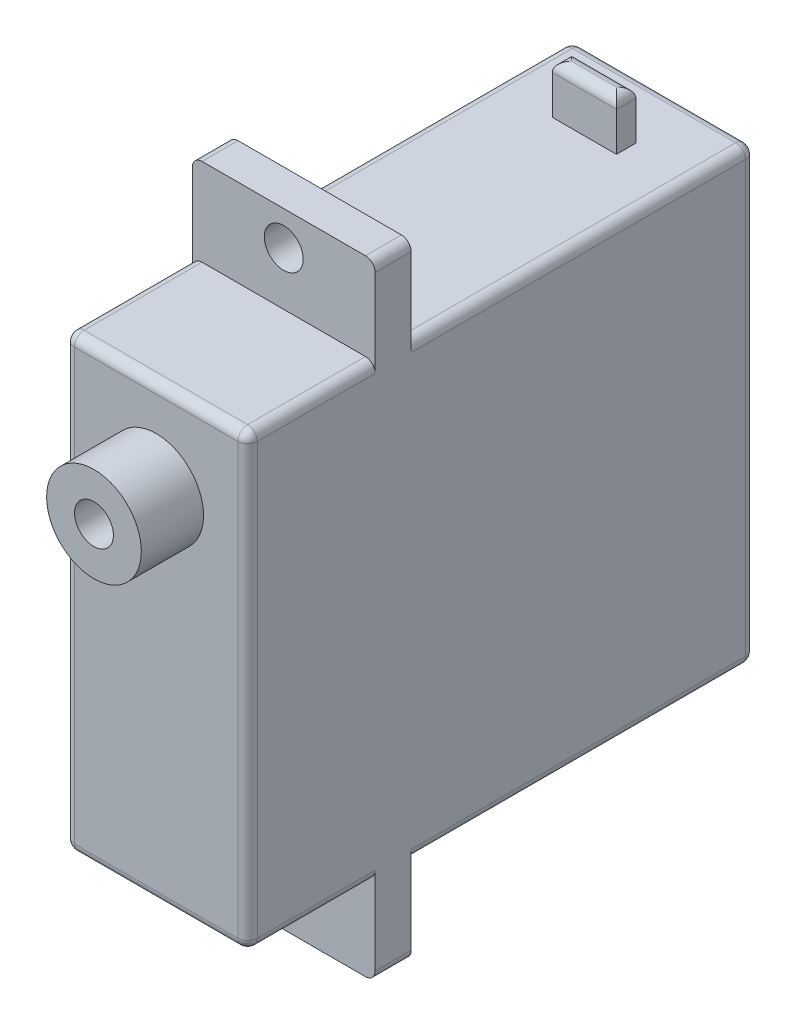
SolidWorks part; units mm, degrees
ref_plane "Front Plane" through (0, 0, 0) normal (0, 0, 1) x (1, 0, 0)
ref_plane "Top Plane" through (0, 0, 0) normal (0, 1, 0) x (1, 0, 0)
ref_plane "Right Plane" through (0, 0, 0) normal (1, 0, 0) x (0, 0, -1)
sketch "Sketch1" plane through (0, 0, 0) normal (1, 0, 0) x (0, 0, -1)
  line L0 (-4.64, 11.565) -> (13.05, 11.565)
  line L1 (-13.05, -11.565) -> (-6.49, -11.565)
  line L2 (-13.05, -11.565) -> (-13.05, 11.565)
  line L3 (-13.05, 11.565) -> (-6.49, 11.565)
  line L4 (13.05, -11.565) -> (13.05, 11.565)
  line L5 (-13.05, -11.565) -> (13.05, 11.565) construction
  line L6 (-13.05, 11.565) -> (13.05, -11.565) construction
  line L8 (-6.49, 11.565) -> (-6.49, 16.055)
  line L9 (-6.49, 16.055) -> (-4.64, 16.055)
  line L10 (-4.64, 11.565) -> (-4.64, 16.055)
  line L11 (-13.05, 0) -> (13.05, 0) construction
  line L12 (-4.64, -11.565) -> (-4.64, -16.055)
  line L13 (-6.49, -16.055) -> (-4.64, -16.055)
  line L14 (-6.49, -11.565) -> (-6.49, -16.055)
  line L15 (-4.64, -11.565) -> (13.05, -11.565)
  point P0 (0, 0)
  dimension "D1" = 23.13
  dimension "D2" = 26.1
  dimension "D3" = 4.49
  dimension "D4" = 1.85
  dimension "D5" = 8.41
extrude "Boss-Extrude1" add sketch "Sketch1" along normal blind 9.4
fillet "Fillet1" radius 0.5 4 edges at (0, -16.055, 5.565) (9.4, -16.055, 5.565) (0, 16.055, 5.565) (9.4, 16.055, 5.565)
fillet "Fillet2" radius 0.5 16 edges at (9.4, -11.565, 9.77) (0, -11.565, 9.77) (0, 11.565, 9.77) (9.4, 11.565, 9.77) (4.7, -11.565, -13.05) (9.4, 0, -13.05) (4.7, 11.565, -13.05) (0, 0, -13.05) (0, -11.565, -4.205) (9.4, -11.565, -4.205) (9.4, 11.565, -4.205) (0, 11.565, -4.205) (4.7, -11.565, 13.05) (4.7, 11.565, 13.05) (0, 0, 13.05) (9.4, 0, 13.05)
sketch "Sketch2" plane through (0, 0, 6.49) normal (0, 0, 1) x (1, 0, 0)
  line L2 (8.9, -16.055) -> (0.5, -16.055) construction
  line L3 (0, 0) -> (9.4, 0) construction
  line L4 (0, -11.065) -> (0, 11.065) construction
  line L5 (9.4, 11.065) -> (9.4, -11.065) construction
  circle A0 centre (4.7, -14.3) radius 1
  circle A3 centre (4.7, 14.3) radius 1
  point P7 (4.7, -16.055)
  dimension "D1" = 2
  dimension "D2" = 14.3
extrude "Cut-Extrude1" cut sketch "Sketch2" against normal through all
sketch "Sketch3" plane through (0, 11.565, 0) normal (0, 1, 0) x (1, 0, 0)
  line L1 (3.05, 9.97) -> (6.35, 9.97)
  line L2 (3.05, 9.97) -> (3.05, 8.97)
  line L3 (3.05, 8.97) -> (6.35, 8.97)
  line L4 (6.35, 9.97) -> (6.35, 8.97)
  line L5 (8.9, 13.05) -> (0.5, 13.05) construction
  line L7 (0.5, 13.05) -> (8.9, 13.05) construction
  line L8 (4.7, 13.05) -> (4.7, 8.97) construction
  point P10 (4.7, 9.97)
  dimension "D1" = 1
  dimension "D2" = 3.08
  dimension "D3" = 3.3
extrude "Boss-Extrude2" add sketch "Sketch3" along normal blind 2.5
fillet "Fillet3" radius 0.5 4 edges at (4.7, 14.065, -9.97) (6.35, 14.065, -9.47) (4.7, 14.065, -8.97) (3.05, 14.065, -9.47)
sketch "Sketch4" plane through (0, 0, 13.05) normal (0, 0, 1) x (1, 0, 0)
  line L1 (8.9, 11.065) -> (0.5, 11.065) construction
  line L2 (0.5, 11.565) -> (8.9, 11.565) construction
  circle A0 centre (4.7, 6.88) radius 2.435
  circle A1 centre (4.7, 6.88) radius 1
  point P8 (4.7, 11.065)
  dimension "D1" = 4.87
  dimension "D2" = 4.685
  dimension "D3" = 2
extrude "Boss-Extrude3" add sketch "Sketch4" along normal blind 3.2
ref_plane "Plane1" through (4.7, 0, 0) normal (-1, 0, 0) x (0, 0, 1)
